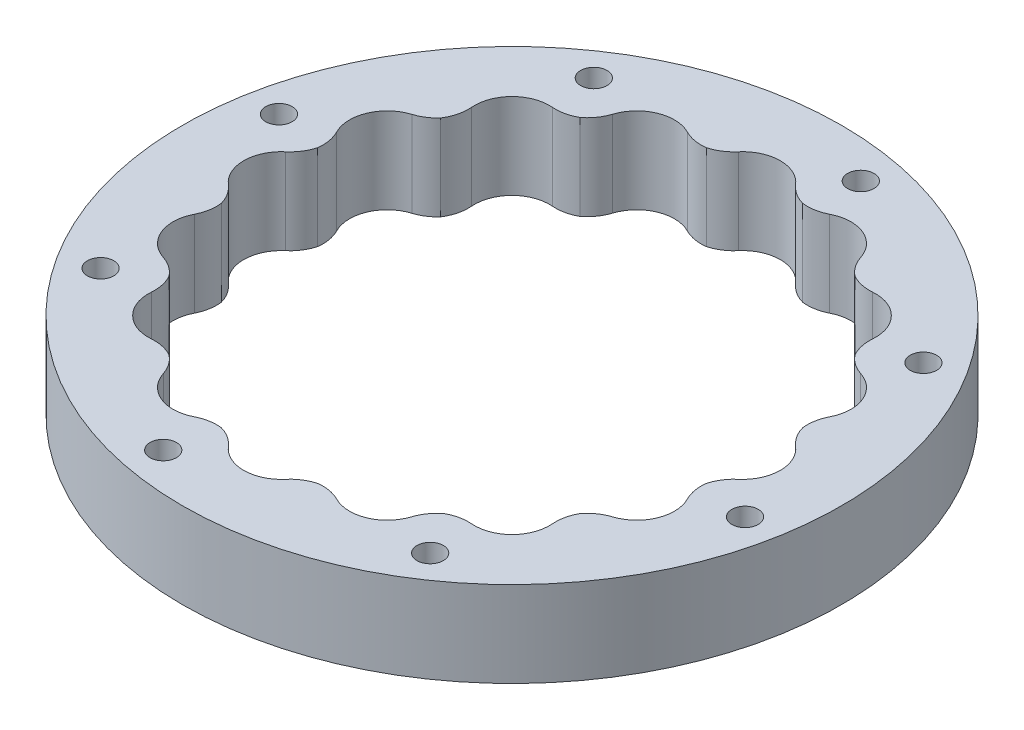
SolidWorks part; units mm, degrees
ref_plane "Front Plane" through (0, 0, 0) normal (0, 0, 1) x (1, 0, 0)
ref_plane "Top Plane" through (0, 0, 0) normal (0, 1, 0) x (1, 0, 0)
ref_plane "Right Plane" through (0, 0, 0) normal (1, 0, 0) x (0, 0, -1)
sketch "Sketch1" plane through (0, 0, 0) normal (0, 1, 0) x (1, 0, 0)
  circle A0 centre (0, 0) radius 35
  circle A1 centre (0, 0) radius 50
  circle A2 centre (0, 0) radius 37.5
  circle A3 centre (0, 35) radius 5.7
  circle A4 centre (13.3939, 32.3358) radius 5.7
  circle A5 centre (24.7487, 24.7487) radius 5.7
  circle A6 centre (32.3358, 13.3939) radius 5.7
  circle A7 centre (35, 0) radius 5.7
  circle A8 centre (32.3358, -13.3939) radius 5.7
  circle A9 centre (24.7487, -24.7487) radius 5.7
  circle A10 centre (13.3939, -32.3358) radius 5.7
  circle A11 centre (0, -35) radius 5.7
  circle A12 centre (-13.3939, -32.3358) radius 5.7
  circle A13 centre (-24.7487, -24.7487) radius 5.7
  circle A14 centre (-32.3358, -13.3939) radius 5.7
  circle A15 centre (-35, 0) radius 5.7
  circle A16 centre (-32.3358, 13.3939) radius 5.7
  circle A17 centre (-24.7487, 24.7487) radius 5.7
  circle A18 centre (-13.3939, 32.3358) radius 5.7
  point P16 (0, 0)
  dimension "D1" = 70
  dimension "D2" = 75
  dimension "D3" = 100
  dimension "D4" = 11.4
  dimension "D5" = 16
extrude "Boss-Extrude1" add sketch "Sketch1" along normal blind 13 contours A1 A18 A2 A3 A4 A5 A6 A7 A8 A9 A10 A11 A12 A13 A14 A15 A16 A17 region at (-48.5858, 0, 0)
fillet "Fillet1" radius 6 31 edges at (-36.3232, 6.5, 9.3208) (-37.1251, 6.5, 5.289) (-37.1251, 6.5, -5.289) (-36.3232, 6.5, -9.3208) (-32.2751, 6.5, 19.0936) (-29.9913, 6.5, 22.5115) (-22.5115, 6.5, 29.9913) (-19.0936, 6.5, 32.2751) (-9.3208, 6.5, 36.3232) (-5.289, 6.5, 37.1251) (5.289, 6.5, 37.1251) (9.3208, 6.5, 36.3232) (19.0936, 6.5, 32.2751) (32.2751, 6.5, 19.0936) (29.9913, 6.5, 22.5115) (22.5115, 6.5, 29.9913) (36.3232, 6.5, 9.3208) (37.1251, 6.5, 5.289) (37.1251, 6.5, -5.289) (36.3232, 6.5, -9.3208) (32.2751, 6.5, -19.0936) (29.9913, 6.5, -22.5115) (22.5115, 6.5, -29.9913) (19.0936, 6.5, -32.2751) (9.3208, 6.5, -36.3232) (5.289, 6.5, -37.1251) (-5.289, 6.5, -37.1251) (-9.3208, 6.5, -36.3232) (-19.0936, 6.5, -32.2751) (-22.5115, 6.5, -29.9913) (-29.9913, 6.5, -22.5115)
fillet "Fillet2" radius 6 1 edges at (-32.2751, 6.5, -19.0936)
sketch "Sketch2" plane through (0, 13, 0) normal (0, 1, 0) x (1, 0, 0)
  line L0 (0, 0) -> (31.1916, 20.8415)
  line L1 (31.1916, 20.8415) -> (37.4161, 25.0007)
  circle A0 centre (0, 0) radius 45
  circle A1 centre (37.4161, 25.0007) radius 2
  dimension "D1" = 90
extrude "Cut-Extrude1" cut sketch "Sketch2" against normal blind 13 contours A1
pattern_circular "CirPattern1" count 8 every 45 about axis through (0, 13, 0) along (0, 1, 0) of "Cut-Extrude1"
equation "\"D_SUN\"=70"
equation "\"D1@Sketch1\"= \"D_SUN\""
equation "\"D_INNER\"=75"
equation "\"D2@Sketch1\"=\"D_INNER\""
equation "\"D_OUTER\"=100"
equation "\"D3@Sketch1\"=\"D_OUTER\""
equation "\"D_BEAR\"= 11.4"
equation "\"D4@Sketch1\"=\"D_BEAR\""
equation "\"G_RATIO\"= 15"
equation "\"D5@Sketch1\"=\"G_RATIO\"+1"
equation "\"D_SCREW\"=90"
equation "\"D1@Sketch2\"= \"D_SCREW\""
equation "\"R_SCREW\"=4"
equation "\"THICK_MID\"= 13"
equation "\"D1@Boss-Extrude1\"=\"THICK_MID\""
equation "\"D2@Sketch2\"=\"R_SCREW\""
equation "\"D1@Cut-Extrude1\"=\"THICK_MID\""
equation "\"D2@CirPattern1\"=360/(8)"
